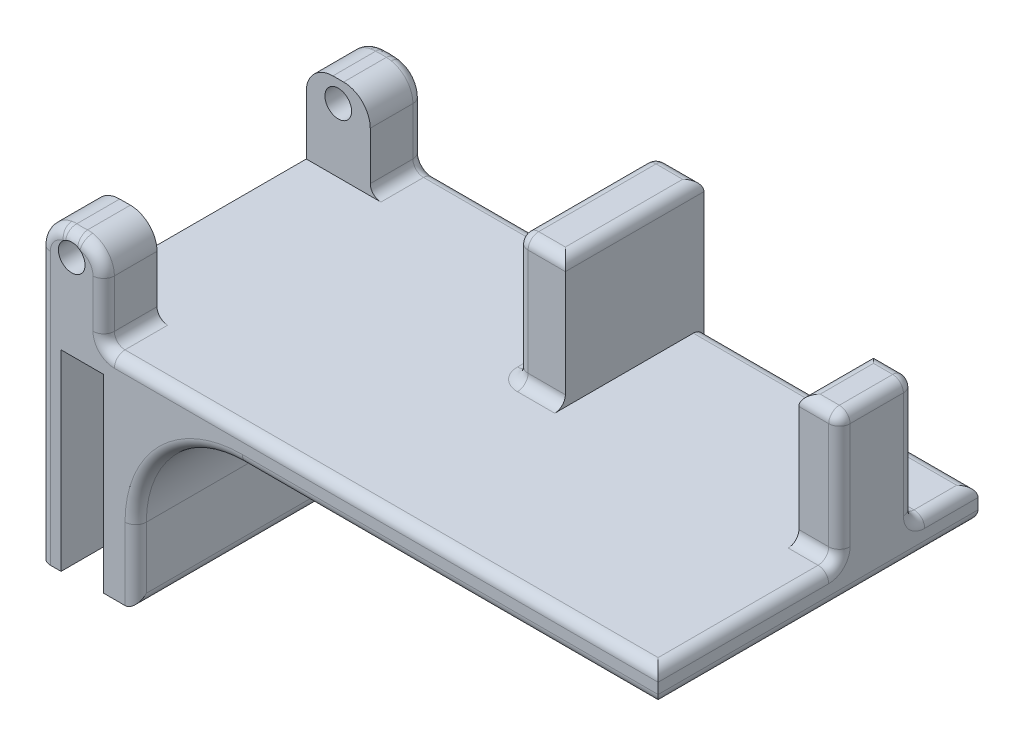
SolidWorks part; units mm, degrees
ref_plane "Front Plane" through (0, 0, 0) normal (0, 0, 1) x (1, 0, 0)
ref_plane "Top Plane" through (0, 0, 0) normal (0, 1, 0) x (1, 0, 0)
ref_plane "Right Plane" through (0, 0, 0) normal (1, 0, 0) x (0, 0, -1)
sketch "Sketch1" plane through (0, 0, 0) normal (0, 0, 1) x (1, 0, 0)
  line L0 (-944.163, 278.3873) -> (-944.163, 296.3873)
  line L1 (-944.163, 181.3873) -> (-944.163, 281.3873) construction
  line L2 (-944.163, 296.3873) -> (-944.163, 280.3873) construction
  line L3 (-944.163, 296.3873) -> (-940.163, 296.3873)
  line L4 (-940.163, 296.3873) -> (-940.163, 278.6136)
  line L5 (-940.163, 296.3873) -> (-940.163, 264.3873) construction
  line L6 (-940.163, 278.6136) -> (-937.163, 278.6136)
  line L7 (-937.163, 278.6136) -> (-937.163, 285.3873)
  line L9 (-946.163, 490.9631) -> (-946.163, 240.9631) construction
  line L10 (-946.163, 298.3873) -> (-946.163, 278.3873)
  line L11 (-946.163, 181.3873) -> (-946.163, 281.3873) construction
  line L12 (-946.163, 278.3873) -> (-944.163, 278.3873)
  line L13 (-940.163, 298.3873) -> (-888.163, 298.3873)
  line L14 (-888.163, 298.3873) -> (-888.163, 295.3873)
  line L15 (-888.163, 295.3873) -> (-927.163, 295.3873)
  line L17 (-946.163, 240.9631) -> (-946.163, 490.9631) construction
  line L19 (-940.163, 304.3873) -> (-940.163, 298.3873)
  line L20 (-943.163, 308.3873) -> (-943.163, 298.3873) construction
  line L21 (-946.163, 304.3873) -> (-946.163, 298.3873)
  line L22 (-946.163, 304.3873) -> (-946.163, 303.8873)
  line L23 (-943.663, 306.3873) -> (-942.663, 306.3873)
  line L24 (-940.163, 303.8873) -> (-940.163, 304.3873)
  arc A0 (-927.163, 295.3873) -> (-937.163, 285.3873) centre (-927.163, 285.3873) ccw
  circle A4 centre (-943.163, 304.3873) radius 1.25
  arc A5 (-943.663, 306.3873) -> (-946.163, 303.8873) centre (-943.663, 303.8873) ccw
  arc A6 (-942.663, 306.3873) -> (-940.163, 303.8873) centre (-942.663, 303.8873) cw
  point P31 (-946.163, 306.3873)
  point P34 (-940.163, 306.3873)
  point P39 (-946.163, 306.3873)
  point P42 (-940.163, 306.3873)
  dimension "D6" = 10
  dimension "D8" = 2.5
  dimension "D9" = 3
  dimension "D1" = 2.5
  dimension "D10" = 52
  dimension "D2" = 3
  dimension "D3" = 20
  dimension "D4" = 20
  dimension "D5" = 3
  dimension "D7" = 8
extrude "Boss-Extrude1" add sketch "Sketch1" along normal blind 15 and the other way blind 15 contours A5 A4 L21 L10 L12 L0 L3 L4 L6 L7 A0 L15 L14 L13 L19 region at (-945.163, 279.0314, 0)
sketch "Sketch2" plane through (0, 0, 0) normal (0, 0, 1) x (1, 0, 0)
  line L1 (-940.163, 298.3873) -> (-955.5918, 298.3873)
  line L2 (-940.163, 298.3873) -> (-940.163, 310.4629)
  line L3 (-940.163, 310.4629) -> (-955.5918, 310.4629)
  line L4 (-955.5918, 298.3873) -> (-955.5918, 310.4629)
extrude "Cut-Extrude1" cut sketch "Sketch2" against normal blind 10 and the other way blind 10
sketch "Sketch3" plane through (0, 298.3873, 0) normal (0, 1, 0) x (1, 0, 0)
  line L0 (-913.663, 2) -> (-917.663, 2) construction
  line L1 (-913.863, 2) -> (-918.363, 2)
  line L2 (-913.863, 2) -> (-913.863, 15)
  line L3 (-913.863, 15) -> (-918.363, 15)
  line L4 (-918.363, 2) -> (-918.363, 15)
  line L5 (-940.163, 15) -> (-888.163, 15) construction
  line L6 (-913.663, 2) -> (-913.663, 15) construction
  line L7 (-888.163, 2) -> (-892.163, 2) construction
  line L9 (-888.163, 9) -> (-888.163, 2)
  line L10 (-888.163, 2) -> (-891.963, 2)
  line L11 (-891.963, 9) -> (-891.963, 2)
  line L12 (-892.163, 2) -> (-892.163, 15) construction
  line L13 (-891.963, 9) -> (-888.163, 9)
  dimension "D1" = 0.2
  dimension "D2" = 4.5
  dimension "D3" = 0.2
  dimension "D4" = 7
extrude "Boss-Extrude2" add sketch "Sketch3" along normal blind 12
fillet "Fillet1" radius 1 39 edges at (-946.163, 291.1373, -15) (-946.163, 291.1373, 15) (-945.4307, 305.6551, -15) (-945.4307, 305.6551, 15) (-940.8952, 305.6551, -15) (-940.8952, 305.6551, 15) (-940.163, 301.1373, -15) (-940.163, 301.1373, 15) (-929.263, 298.3873, -15) (-916.113, 298.3873, -2) (-934.234, 292.4584, -15) (-934.234, 292.4584, 15) (-937.163, 282.0005, -15) (-937.163, 278.6136, 0) (-937.163, 282.0005, 15) (-907.663, 295.3873, -15) (-907.663, 295.3873, 15) (-888.163, 295.3873, 0) (-916.113, 310.3873, -2) (-918.363, 310.3873, -8.5) (-916.113, 310.3873, -15) (-913.863, 310.3873, -8.5) (-890.063, 310.3873, -9) (-888.163, 310.3873, -5.5) (-890.063, 310.3873, -2) (-891.963, 310.3873, -5.5) (-940.163, 298.3873, -12.5) (-940.163, 298.3873, 12.5) (-890.063, 298.3873, -9) (-890.063, 298.3873, -2) (-918.363, 298.3873, -8.5) (-918.363, 304.3873, -15) (-918.363, 304.3873, -2) (-888.163, 304.3873, -2) (-888.163, 304.3873, -9) (-901.013, 298.3873, -15) (-888.163, 298.3873, -12) (-888.163, 298.3873, 6.5) (-914.163, 298.3873, 15)
